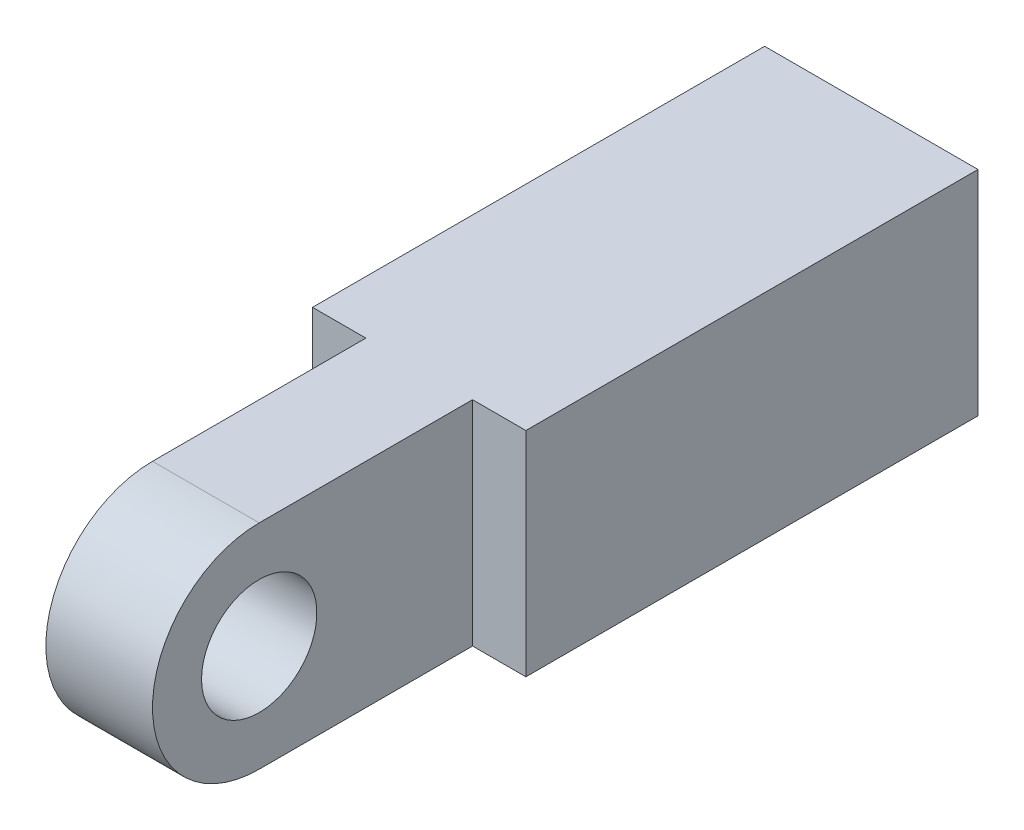
SolidWorks part; units mm, degrees
ref_plane "Front Plane" through (0, 0, 0) normal (0, 0, 1) x (1, 0, 0)
ref_plane "Top Plane" through (0, 0, 0) normal (0, 1, 0) x (1, 0, 0)
ref_plane "Right Plane" through (0, 0, 0) normal (1, 0, 0) x (0, 0, -1)
sketch "Sketch2" plane through (0, 0, 0) normal (0, 0, 1) x (1, 0, 0)
  line L1 (-21, 21) -> (21, 21)
  line L2 (-21, 21) -> (-21, -21)
  line L3 (-21, -21) -> (21, -21)
  line L4 (21, 21) -> (21, -21)
  line L5 (-21, 21) -> (21, -21) construction
  line L6 (-21, -21) -> (21, 21) construction
  point P0 (0, 0)
  dimension "D1" = 42
  dimension "D2" = 42
extrude "Boss-Extrude1" add sketch "Sketch2" along normal blind 89
ref_plane "Plane1" through (0, 0, 89) normal (0, 0, 1) x (1, 0, 0)
sketch "Sketch3" plane through (0, 0, 89) normal (0, 0, 1) x (1, 0, 0)
  line L0 (21, 21) -> (-21, 21) construction
  line L1 (10.5, -21) -> (-10.5, -21)
  line L2 (10.5, -21) -> (10.5, 21)
  line L3 (10.5, 21) -> (-10.5, 21)
  line L4 (-10.5, -21) -> (-10.5, 21)
  line L5 (10.5, -21) -> (-10.5, 21) construction
  line L6 (10.5, 21) -> (-10.5, -21) construction
  point P0 (0, 0)
  dimension "D1" = 21
ref_plane "Plane4" through (0, 0, 0) normal (0, 0, -1) x (-1, 0, 0)
sketch "Sketch7" plane through (0, 0, 0) normal (0, 0, -1) x (-1, 0, 0)
  line L0 (21, 21) -> (21, -21) construction
  line L1 (-16, 16) -> (16, 16)
  line L2 (-16, 16) -> (-16, -16)
  line L3 (-16, -16) -> (16, -16)
  line L4 (16, 16) -> (16, -16)
  line L5 (-16, 16) -> (16, -16) construction
  line L6 (-16, -16) -> (16, 16) construction
  line L7 (-21, 21) -> (21, 21) construction
  point P0 (0, 0)
  dimension "D1" = 5
  dimension "D2" = 5
extrude "Cut-Extrude1" cut sketch "Sketch7" against normal blind 81 contours L4 L3 L2 L1
extrude "Boss-Extrude2" add sketch "Sketch3" along normal blind 42
ref_plane "Plane5" through (-10.5, 0, 0) normal (-1, 0, 0) x (0, 0, 1)
sketch "Sketch8" plane through (-10.5, 0, 0) normal (-1, 0, 0) x (0, 0, 1)
  line L0 (131, 21) -> (131, -21) construction
  line L1 (131, 21) -> (131, -21)
  arc A0 (131, 21) -> (131, -21) centre (131, 0) cw
  dimension "D1" = 21
extrude "Boss-Extrude3" add sketch "Sketch8" against normal blind 21
ref_plane "Plane6" through (-10.5, 0, 0) normal (-1, 0, 0) x (0, 0, 1)
sketch "Sketch9" plane through (-10.5, 0, 0) normal (-1, 0, 0) x (0, 0, 1)
  line L0 (89, 21) -> (89, -21) construction
  line L1 (131, 21) -> (131, -21)
  circle A0 centre (131, 0) radius 11.35
  dimension "D1" = 42
  dimension "D2" = 22.7
extrude "Cut-Extrude2" cut sketch "Sketch9" against normal through all contours A0
